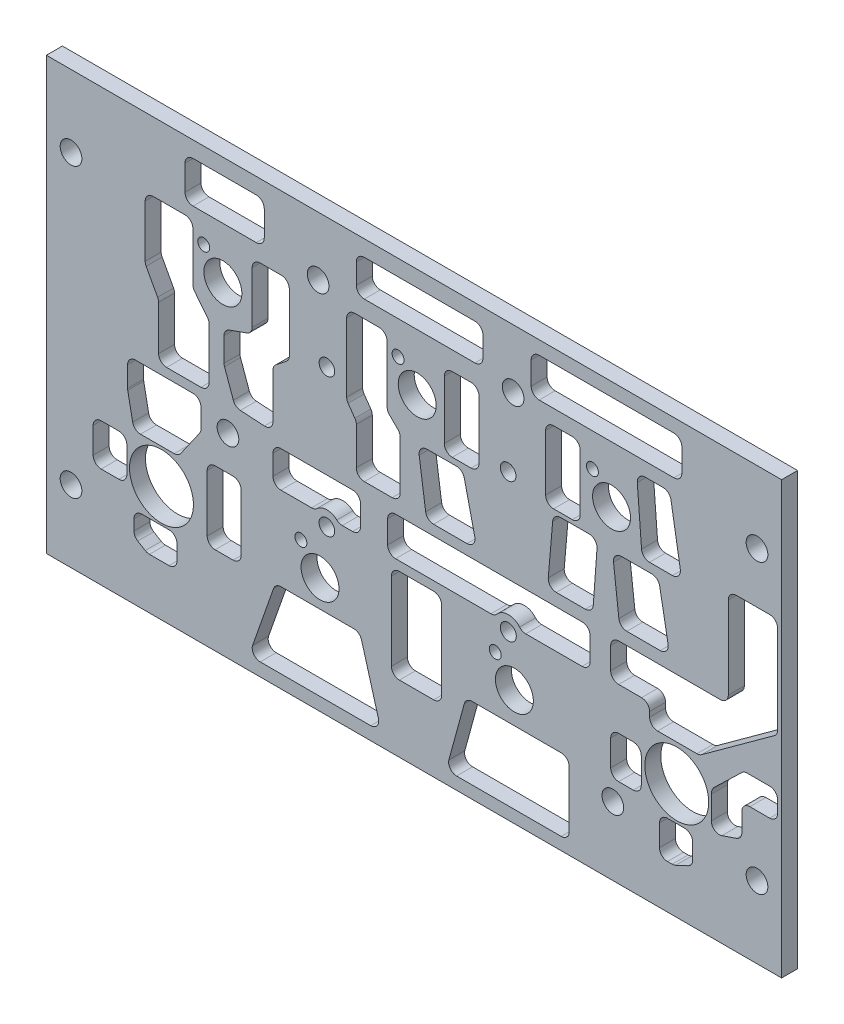
SolidWorks part; units mm, degrees
ref_plane "Front Plane" through (0, 0, 0) normal (0, 0, 1) x (1, 0, 0)
ref_plane "Top Plane" through (0, 0, 0) normal (0, 1, 0) x (1, 0, 0)
ref_plane "Right Plane" through (0, 0, 0) normal (1, 0, 0) x (0, 0, -1)
sketch "Sketch1" plane through (0, 0, 0) normal (0, 0, 1) x (1, 0, 0)
  line L4 (0, 85.725) -> (-146.05, 85.725)
  line L5 (-146.05, 85.725) -> (-146.05, 0)
  line L6 (-146.05, 0) -> (0, 0)
  line L7 (0, 0) -> (0, 85.725)
  line L8 (0, 85.725) -> (-146.05, 85.725)
  line L9 (-146.05, 85.725) -> (-146.05, 0)
  line L10 (-146.05, 0) -> (0, 0)
  line L11 (0, 0) -> (0, 85.725)
  dimension "D1" = 0
extrude "Backplate Body" add sketch "Sketch1" against normal blind 3.175
hole_wizard "#6 Clearance Hole1" positions "Sketch3" profile "Sketch2" hole size "#6" standard "ANSI Inch"
sketch "Sketch3" plane through (0, 0, -3.175) normal (0, 0, -1) x (-1, 0, 0)
  point P0 (4.8895, 71.4375)
  point P3 (53.34, 74.041)
  point P6 (92.075, 74.041)
  point P9 (141.1605, 71.4375)
  point P12 (109.982, 38.735)
  point P15 (141.1605, 14.2875)
  point P18 (33.528, 13.589)
  point P21 (4.8895, 14.2875)
sketch "Sketch2" plane through (-4.8895, 71.4375, -3.175) normal (1, 0, 0) x (0, 1, 0)
  line L0 (0, 0) -> (0, 13.9934)
  line L1 (0, 13.9934) -> (2.1526, 12.7)
  line L2 (2.1526, 12.7) -> (2.1526, 0)
  line L5 (2.1526, 0) -> (0, 0)
  line L10 (0, 13.9934) -> (-2.1526, 12.7) construction
  line L11 (0, -6.35) -> (0, 107.95) construction
  dimension "Hole Dia." = 4.3053
  dimension "Hole Depth" = 12.7
  dimension "Drill Angle" = 118
sketch "Sketch4" plane through (0, 0, -3.175) normal (0, 0, -1) x (-1, 0, 0)
  circle A0 centre (20.828, 22.987) radius 6.35
  circle A1 centre (123.19, 22.987) radius 6.35
  circle A2 centre (33.782, 64.135) radius 3.7703
  circle A3 centre (72.39, 64.135) radius 3.7703
  circle A4 centre (110.998, 64.135) radius 3.7703
  circle A5 centre (91.694, 22.987) radius 3.7703
  circle A6 centre (53.086, 22.987) radius 3.7703
  circle A7 centre (37.5823, 68.778) radius 1.1906
  circle A8 centre (76.1903, 68.778) radius 1.1906
  circle A9 centre (114.7983, 68.778) radius 1.1906
  circle A10 centre (56.8863, 27.63) radius 1.1906
  circle A11 centre (95.4943, 27.63) radius 1.1906
  dimension "D1" = 12.7
  dimension "D2" = 7.5406
  dimension "D3" = 2.3813
extrude "Switch Mount Holes" cut sketch "Sketch4" against normal through all
sketch "Sketch6" plane through (0, 0, -3.175) normal (0, 0, -1) x (-1, 0, 0)
  line L0 (0.7854, 59.7497) -> (0.7854, 42.2627)
  line L1 (1.4397, 40.9784) -> (15.8873, 30.4799)
  line L4 (16.8205, 30.1766) -> (24.6388, 30.1766)
  line L5 (26.2263, 31.7641) -> (26.2263, 32.7329)
  line L6 (27.8138, 34.3204) -> (32.3673, 34.3204)
  line L7 (33.9548, 35.9079) -> (33.9548, 40.2156)
  line L8 (32.3673, 41.8031) -> (12.1743, 41.8031)
  line L9 (10.5868, 43.3906) -> (10.5868, 59.7497)
  line L10 (8.9993, 61.3372) -> (2.3729, 61.3372)
  line L11 (21.4, 75.3506) -> (48.1668, 75.3506)
  line L12 (49.7543, 76.9381) -> (49.7543, 81.4624)
  line L13 (48.1668, 83.0499) -> (21.4, 83.0499)
  line L14 (19.8125, 81.4624) -> (19.8125, 76.9381)
  line L15 (59.3356, 80.9492) -> (59.3356, 76.9381)
  line L16 (60.9231, 75.3506) -> (82.8992, 75.3506)
  line L17 (84.4867, 76.9381) -> (84.4867, 80.9492)
  line L18 (82.8992, 82.5367) -> (60.9231, 82.5367)
  line L19 (28.672, 70.9074) -> (27.8272, 59.8641)
  line L20 (26.2443, 58.3977) -> (21.6898, 58.3977)
  line L21 (20.1244, 60.2489) -> (21.9848, 71.2922)
  line L22 (23.5503, 72.616) -> (27.0892, 72.616)
  line L23 (46.8767, 70.769) -> (46.8767, 59.6575)
  line L24 (45.2892, 58.07) -> (41.5893, 58.07)
  line L25 (40.0018, 59.6575) -> (40.0018, 70.769)
  line L26 (41.5893, 72.3565) -> (45.2892, 72.3565)
  line L27 (38.2576, 57.2789) -> (43.8996, 57.2789)
  line L28 (45.4813, 55.8276) -> (46.355, 45.6783)
  line L29 (44.7734, 43.9546) -> (38.997, 43.9546)
  line L30 (37.4137, 45.4268) -> (36.6743, 55.5761)
  line L31 (24.2194, 55.3227) -> (22.5486, 46.1448)
  line L32 (24.1104, 44.273) -> (30.7553, 44.273)
  line L33 (32.3322, 45.6779) -> (33.3948, 54.8558)
  line L34 (31.8178, 56.6259) -> (25.7812, 56.6259)
  line L35 (61.6963, 71.619) -> (65.4237, 71.619)
  line L36 (67.0112, 70.0315) -> (67.0112, 58.4598)
  line L37 (65.4237, 56.8723) -> (61.6963, 56.8723)
  line L38 (60.1088, 58.4598) -> (60.1088, 70.0315)
  line L39 (78.3684, 70.3657) -> (78.3684, 59.0552)
  line L40 (77.9034, 57.9327) -> (76.2306, 56.2599)
  line L41 (75.7657, 55.1374) -> (75.7657, 45.5421)
  line L42 (77.3532, 43.9546) -> (82.8992, 43.9546)
  line L43 (84.4867, 45.5421) -> (84.4867, 52.9982)
  line L44 (84.774, 53.9091) -> (86.1126, 55.8195)
  line L45 (86.3999, 56.7304) -> (86.3999, 70.3657)
  line L46 (84.8124, 71.9532) -> (79.9559, 71.9532)
  line L47 (64.5881, 55.7521) -> (70.4272, 55.7521)
  line L48 (71.9989, 53.9418) -> (70.7103, 44.8514)
  line L49 (69.1385, 43.4867) -> (62.4983, 43.4867)
  line L50 (60.9512, 45.4299) -> (63.041, 54.5203)
  line L51 (104.3617, 82.5367) -> (116.9306, 82.5367)
  line L52 (118.5181, 80.9492) -> (118.5181, 75.9239)
  line L53 (116.9306, 74.3364) -> (104.3617, 74.3364)
  line L54 (102.7742, 75.9239) -> (102.7742, 80.9492)
  line L55 (116.9515, 70.4508) -> (116.9515, 60.795)
  line L56 (116.6029, 59.8023) -> (114.0887, 56.6647)
  line L57 (113.7401, 55.6721) -> (113.7401, 45.5421)
  line L58 (115.3276, 43.9546) -> (122.1785, 43.9546)
  line L59 (123.766, 45.5421) -> (123.766, 54.3743)
  line L60 (123.9579, 55.131) -> (126.2372, 59.3351)
  line L61 (126.4292, 60.0918) -> (126.4292, 70.4508)
  line L62 (124.8417, 72.0383) -> (118.539, 72.0383)
  line L63 (105.1722, 69.6262) -> (105.1722, 59.351)
  line L64 (106.2241, 57.8565) -> (109.7117, 56.6066)
  line L65 (110.7636, 55.1122) -> (110.7636, 50.368)
  line L66 (110.6706, 49.8324) -> (108.9167, 44.9385)
  line L67 (107.5209, 43.8896) -> (102.7372, 43.5917)
  line L68 (101.051, 45.1761) -> (101.051, 54.0148)
  line L69 (100.4562, 55.2536) -> (98.3918, 56.9078)
  line L70 (97.797, 58.1467) -> (97.797, 69.6262)
  line L71 (99.3845, 71.2137) -> (103.5847, 71.2137)
  line L72 (39.6269, 33.7908) -> (50.842, 33.7908)
  line L73 (78.2665, 35.3783) -> (78.2665, 39.8664)
  line L74 (76.679, 41.4539) -> (39.6269, 41.4539)
  line L75 (38.0394, 39.8664) -> (38.0394, 35.3783)
  line L76 (83.642, 39.7608) -> (83.642, 35.7883)
  line L77 (85.2295, 34.2008) -> (87.2841, 34.2008)
  line L78 (101.051, 35.7883) -> (101.051, 39.7608)
  line L79 (99.4635, 41.3483) -> (85.2295, 41.3483)
  line L80 (115.3458, 40.5393) -> (115.3458, 36.8018)
  line L81 (115.6328, 35.8915) -> (119.3681, 30.5551)
  line L82 (120.6686, 29.8779) -> (127.3572, 29.8779)
  line L83 (128.9152, 31.1612) -> (129.8894, 36.1507)
  line L84 (129.9188, 36.4549) -> (129.9188, 40.5393)
  line L85 (128.3313, 42.1268) -> (116.9333, 42.1268)
  line L86 (0.7854, 30.2344) -> (0.7854, 27.9015)
  line L87 (2.3729, 26.314) -> (6.3156, 26.314)
  line L88 (7.9031, 24.7265) -> (7.9031, 21.0409)
  line L91 (13.9709, 20.0555) -> (13.9709, 24.6575)
  line L92 (13.3361, 26.1523) -> (7.9216, 31.3768)
  line L93 (6.8193, 31.8219) -> (2.3729, 31.8219)
  line L94 (18.5828, 10.0167) -> (21.0703, 8.8579)
  line L95 (21.7407, 8.7095) -> (22.6736, 8.7095)
  line L96 (24.2611, 10.297) -> (24.2611, 14.5475)
  line L97 (22.6736, 16.135) -> (19.2531, 16.135)
  line L98 (17.6656, 14.5475) -> (17.6656, 11.4558)
  line L99 (27.8819, 24.3095) -> (27.8819, 19.1834)
  line L100 (29.4694, 17.5959) -> (32.3673, 17.5959)
  line L101 (33.9548, 19.1834) -> (33.9548, 24.3095)
  line L102 (32.3673, 25.897) -> (29.4694, 25.897)
  line L103 (43.7793, 2.4684) -> (64.5682, 2.4684)
  line L104 (66.0995, 4.4745) -> (63.0373, 15.675)
  line L105 (61.506, 16.8438) -> (43.7793, 16.8438)
  line L106 (42.1918, 15.2563) -> (42.1918, 4.0559)
  line L107 (67.5359, 30.389) -> (67.5359, 14.8805)
  line L108 (69.1234, 13.293) -> (75.9295, 13.293)
  line L109 (77.517, 14.8805) -> (77.517, 30.389)
  line L110 (75.9295, 31.9765) -> (69.1234, 31.9765)
  line L111 (83.4506, 16.4411) -> (80.1004, 4.6154)
  line L112 (81.6278, 2.5952) -> (103.578, 2.5952)
  line L113 (105.0761, 4.708) -> (100.9298, 16.5336)
  line L114 (99.4317, 17.5959) -> (84.978, 17.5959)
  line L115 (114.1111, 30.2647) -> (114.1111, 18.9987)
  line L116 (112.5236, 17.4112) -> (108.9618, 17.4112)
  line L117 (107.3743, 18.9987) -> (107.3743, 30.2647)
  line L118 (108.9618, 31.8522) -> (112.5236, 31.8522)
  line L119 (130.0717, 26.6877) -> (130.0717, 21.5613)
  line L120 (131.6592, 19.9738) -> (135.1785, 19.9738)
  line L121 (136.766, 21.5613) -> (136.766, 26.6877)
  line L122 (135.1785, 28.2752) -> (131.6592, 28.2752)
  line L123 (121.6942, 16.2539) -> (127.0772, 16.2539)
  line L124 (128.6647, 14.6664) -> (128.6647, 12.5851)
  line L125 (127.9016, 11.2285) -> (126.4171, 10.3264)
  line L126 (125.5927, 10.0955) -> (121.6942, 10.0955)
  line L127 (120.1067, 11.683) -> (120.1067, 14.6664)
  line L129 (57.7397, 33.7908) -> (76.679, 33.7908)
  line L130 (93.3749, 34.2008) -> (99.4635, 34.2008)
  line L131 (8.9787, 19.5382) -> (11.8715, 18.5528)
  line L132 (0.0043, 85.727) -> (146.0543, 85.727) construction
  line L133 (0.0043, 85.727) -> (0.0043, 0.002) construction
  arc A0 (121.6942, 10.0955) -> (120.1067, 11.683) centre (121.6942, 11.683) cw
  arc A1 (126.4171, 10.3264) -> (125.5927, 10.0955) centre (125.5927, 11.683) cw
  arc A2 (128.6647, 12.5851) -> (127.9016, 11.2285) centre (127.0772, 12.5851) cw
  arc A3 (127.0772, 16.2539) -> (128.6647, 14.6664) centre (127.0772, 14.6664) cw
  arc A4 (136.766, 26.6877) -> (135.1785, 28.2752) centre (135.1785, 26.6877) ccw
  arc A5 (121.6942, 16.2539) -> (120.1067, 14.6664) centre (121.6942, 14.6664) ccw
  arc A6 (135.1785, 19.9738) -> (136.766, 21.5613) centre (135.1785, 21.5613) ccw
  arc A7 (130.0717, 21.5613) -> (131.6592, 19.9738) centre (131.6592, 21.5613) ccw
  arc A8 (130.0717, 26.6877) -> (131.6592, 28.2752) centre (131.6592, 26.6877) cw
  arc A9 (107.3743, 30.2647) -> (108.9618, 31.8522) centre (108.9618, 30.2647) cw
  arc A10 (108.9618, 17.4112) -> (107.3743, 18.9987) centre (108.9618, 18.9987) cw
  arc A11 (114.1111, 18.9987) -> (112.5236, 17.4112) centre (112.5236, 18.9987) cw
  arc A12 (114.1111, 30.2647) -> (112.5236, 31.8522) centre (112.5236, 30.2647) ccw
  arc A13 (103.578, 2.5952) -> (105.0761, 4.708) centre (103.578, 4.1827) ccw
  arc A14 (100.9298, 16.5336) -> (99.4317, 17.5959) centre (99.4317, 16.0084) ccw
  arc A15 (80.1004, 4.6154) -> (81.6278, 2.5952) centre (81.6278, 4.1827) ccw
  arc A16 (83.4506, 16.4411) -> (84.978, 17.5959) centre (84.978, 16.0084) cw
  arc A17 (77.517, 30.389) -> (75.9295, 31.9765) centre (75.9295, 30.389) ccw
  arc A18 (75.9295, 13.293) -> (77.517, 14.8805) centre (75.9295, 14.8805) ccw
  arc A19 (67.5359, 14.8805) -> (69.1234, 13.293) centre (69.1234, 14.8805) ccw
  arc A20 (43.7793, 16.8438) -> (42.1918, 15.2563) centre (43.7793, 15.2563) ccw
  arc A21 (63.0373, 15.675) -> (61.506, 16.8438) centre (61.506, 15.2563) ccw
  arc A22 (67.5359, 30.389) -> (69.1234, 31.9765) centre (69.1234, 30.389) cw
  arc A23 (64.5682, 2.4684) -> (66.0995, 4.4745) centre (64.5682, 4.0559) ccw
  arc A24 (43.7793, 2.4684) -> (42.1918, 4.0559) centre (43.7793, 4.0559) cw
  arc A25 (32.3673, 17.5959) -> (33.9548, 19.1834) centre (32.3673, 19.1834) ccw
  arc A26 (33.9548, 24.3095) -> (32.3673, 25.897) centre (32.3673, 24.3095) ccw
  arc A27 (27.8819, 19.1834) -> (29.4694, 17.5959) centre (29.4694, 19.1834) ccw
  arc A28 (27.8819, 24.3095) -> (29.4694, 25.897) centre (29.4694, 24.3095) cw
  arc A29 (19.2531, 16.135) -> (17.6656, 14.5475) centre (19.2531, 14.5475) ccw
  arc A30 (24.2611, 14.5475) -> (22.6736, 16.135) centre (22.6736, 14.5475) ccw
  arc A31 (22.6736, 8.7095) -> (24.2611, 10.297) centre (22.6736, 10.297) ccw
  arc A32 (21.0703, 8.8579) -> (21.7407, 8.7095) centre (21.7407, 10.297) ccw
  arc A33 (18.5828, 10.0167) -> (17.6656, 11.4558) centre (19.2531, 11.4558) cw
  arc A34 (7.9216, 31.3768) -> (6.8193, 31.8219) centre (6.8193, 30.2344) ccw
  arc A37 (13.9709, 24.6575) -> (13.3361, 26.1523) centre (11.8938, 24.6575) ccw
  arc A39 (6.3156, 26.314) -> (7.9031, 24.7265) centre (6.3156, 24.7265) cw
  arc A40 (0.7854, 27.9015) -> (2.3729, 26.314) centre (2.3729, 27.9015) ccw
  arc A41 (0.7854, 30.2344) -> (2.3729, 31.8219) centre (2.3729, 30.2344) cw
  arc A42 (129.9188, 40.5393) -> (128.3313, 42.1268) centre (128.3313, 40.5393) ccw
  arc A43 (127.3572, 29.8779) -> (128.9152, 31.1612) centre (127.3572, 31.4654) ccw
  arc A44 (129.8894, 36.1507) -> (129.9188, 36.4549) centre (128.3313, 36.4549) ccw
  arc A45 (119.3681, 30.5551) -> (120.6686, 29.8779) centre (120.6686, 31.4654) ccw
  arc A46 (115.3458, 36.8018) -> (115.6328, 35.8915) centre (116.9333, 36.8018) ccw
  arc A47 (115.3458, 40.5393) -> (116.9333, 42.1268) centre (116.9333, 40.5393) cw
  arc A48 (99.4635, 34.2008) -> (101.051, 35.7883) centre (99.4635, 35.7883) ccw
  arc A49 (101.051, 39.7608) -> (99.4635, 41.3483) centre (99.4635, 39.7608) ccw
  arc A50 (83.642, 35.7883) -> (85.2295, 34.2008) centre (85.2295, 35.7883) ccw
  arc A51 (83.642, 39.7608) -> (85.2295, 41.3483) centre (85.2295, 39.7608) cw
  arc A52 (39.6269, 41.4539) -> (38.0394, 39.8664) centre (39.6269, 39.8664) ccw
  arc A53 (78.2665, 39.8664) -> (76.679, 41.4539) centre (76.679, 39.8664) ccw
  arc A54 (76.679, 33.7908) -> (78.2665, 35.3783) centre (76.679, 35.3783) ccw
  arc A55 (39.6269, 33.7908) -> (38.0394, 35.3783) centre (39.6269, 35.3783) cw
  arc A56 (97.797, 69.6262) -> (99.3845, 71.2137) centre (99.3845, 69.6262) cw
  arc A57 (98.3918, 56.9078) -> (97.797, 58.1467) centre (99.3845, 58.1467) cw
  arc A58 (102.7372, 43.5917) -> (101.051, 45.1761) centre (102.6385, 45.1761) cw
  arc A59 (101.051, 54.0148) -> (100.4562, 55.2536) centre (99.4635, 54.0148) ccw
  arc A60 (110.7636, 50.368) -> (110.6706, 49.8324) centre (109.1761, 50.368) cw
  arc A61 (108.9167, 44.9385) -> (107.5209, 43.8896) centre (107.4222, 45.4741) cw
  arc A62 (109.7117, 56.6066) -> (110.7636, 55.1122) centre (109.1761, 55.1122) cw
  arc A63 (105.1722, 59.351) -> (106.2241, 57.8565) centre (106.7597, 59.351) ccw
  arc A64 (126.4292, 70.4508) -> (124.8417, 72.0383) centre (124.8417, 70.4508) ccw
  arc A65 (126.2372, 59.3351) -> (126.4292, 60.0918) centre (124.8417, 60.0918) ccw
  arc A66 (105.1722, 69.6262) -> (103.5847, 71.2137) centre (103.5847, 69.6262) ccw
  arc A67 (122.1785, 43.9546) -> (123.766, 45.5421) centre (122.1785, 45.5421) ccw
  arc A68 (113.7401, 45.5421) -> (115.3276, 43.9546) centre (115.3276, 45.5421) ccw
  arc A69 (114.0887, 56.6647) -> (113.7401, 55.6721) centre (115.3276, 55.6721) ccw
  arc A70 (123.766, 54.3743) -> (123.9579, 55.131) centre (125.3535, 54.3743) cw
  arc A71 (116.9515, 60.795) -> (116.6029, 59.8023) centre (115.364, 60.795) cw
  arc A72 (116.9515, 70.4508) -> (118.539, 72.0383) centre (118.539, 70.4508) cw
  arc A73 (104.3617, 74.3364) -> (102.7742, 75.9239) centre (104.3617, 75.9239) cw
  arc A74 (118.5181, 75.9239) -> (116.9306, 74.3364) centre (116.9306, 75.9239) cw
  arc A75 (116.9306, 82.5367) -> (118.5181, 80.9492) centre (116.9306, 80.9492) cw
  arc A76 (104.3617, 82.5367) -> (102.7742, 80.9492) centre (104.3617, 80.9492) ccw
  arc A77 (62.4983, 43.4867) -> (60.9512, 45.4299) centre (62.4983, 45.0742) cw
  arc A78 (70.7103, 44.8514) -> (69.1385, 43.4867) centre (69.1385, 45.0742) cw
  arc A79 (70.4272, 55.7521) -> (71.9989, 53.9418) centre (70.4272, 54.1646) cw
  arc A80 (86.3999, 70.3657) -> (84.8124, 71.9532) centre (84.8124, 70.3657) ccw
  arc A81 (64.5881, 55.7521) -> (63.041, 54.5203) centre (64.5881, 54.1646) ccw
  arc A82 (86.1126, 55.8195) -> (86.3999, 56.7304) centre (84.8124, 56.7304) ccw
  arc A83 (82.8992, 43.9546) -> (84.4867, 45.5421) centre (82.8992, 45.5421) ccw
  arc A84 (75.7657, 45.5421) -> (77.3532, 43.9546) centre (77.3532, 45.5421) ccw
  arc A85 (65.4237, 71.619) -> (67.0112, 70.0315) centre (65.4237, 70.0315) cw
  arc A86 (61.6963, 71.619) -> (60.1088, 70.0315) centre (61.6963, 70.0315) ccw
  arc A87 (76.2306, 56.2599) -> (75.7657, 55.1374) centre (77.3532, 55.1374) ccw
  arc A88 (84.4867, 52.9982) -> (84.774, 53.9091) centre (86.0742, 52.9982) cw
  arc A89 (78.3684, 59.0552) -> (77.9034, 57.9327) centre (76.7809, 59.0552) cw
  arc A90 (78.3684, 70.3657) -> (79.9559, 71.9532) centre (79.9559, 70.3657) cw
  arc A91 (61.6963, 56.8723) -> (60.1088, 58.4598) centre (61.6963, 58.4598) cw
  arc A92 (67.0112, 58.4598) -> (65.4237, 56.8723) centre (65.4237, 58.4598) cw
  arc A93 (33.3948, 54.8558) -> (31.8178, 56.6259) centre (31.8178, 55.0384) ccw
  arc A94 (30.7553, 44.273) -> (32.3322, 45.6779) centre (30.7553, 45.8605) ccw
  arc A95 (22.5486, 46.1448) -> (24.1104, 44.273) centre (24.1104, 45.8605) ccw
  arc A96 (24.2194, 55.3227) -> (25.7812, 56.6259) centre (25.7812, 55.0384) cw
  arc A97 (46.355, 45.6783) -> (44.7734, 43.9546) centre (44.7734, 45.5421) cw
  arc A98 (38.997, 43.9546) -> (37.4137, 45.4268) centre (38.997, 45.5421) cw
  arc A99 (43.8996, 57.2789) -> (45.4813, 55.8276) centre (43.8996, 55.6914) cw
  arc A100 (38.2576, 57.2789) -> (36.6743, 55.5761) centre (38.2576, 55.6914) ccw
  arc A101 (40.0018, 70.769) -> (41.5893, 72.3565) centre (41.5893, 70.769) cw
  arc A102 (41.5893, 58.07) -> (40.0018, 59.6575) centre (41.5893, 59.6575) cw
  arc A103 (46.8767, 59.6575) -> (45.2892, 58.07) centre (45.2892, 59.6575) cw
  arc A104 (21.9848, 71.2922) -> (23.5503, 72.616) centre (23.5503, 71.0285) cw
  arc A105 (21.6898, 58.3977) -> (20.1244, 60.2489) centre (21.6898, 59.9852) cw
  arc A106 (46.8767, 70.769) -> (45.2892, 72.3565) centre (45.2892, 70.769) ccw
  arc A107 (27.8272, 59.8641) -> (26.2443, 58.3977) centre (26.2443, 59.9852) cw
  arc A108 (28.672, 70.9074) -> (27.0892, 72.616) centre (27.0892, 71.0285) ccw
  arc A109 (84.4867, 80.9492) -> (82.8992, 82.5367) centre (82.8992, 80.9492) ccw
  arc A110 (59.3356, 76.9381) -> (60.9231, 75.3506) centre (60.9231, 76.9381) ccw
  arc A111 (82.8992, 75.3506) -> (84.4867, 76.9381) centre (82.8992, 76.9381) ccw
  arc A112 (10.5868, 59.7497) -> (8.9993, 61.3372) centre (8.9993, 59.7497) ccw
  arc A113 (12.1743, 41.8031) -> (10.5868, 43.3906) centre (12.1743, 43.3906) cw
  arc A114 (32.3673, 34.3204) -> (33.9548, 35.9079) centre (32.3673, 35.9079) ccw
  arc A115 (33.9548, 40.2156) -> (32.3673, 41.8031) centre (32.3673, 40.2156) ccw
  arc A116 (24.6388, 30.1766) -> (26.2263, 31.7641) centre (24.6388, 31.7641) ccw
  arc A117 (26.2263, 32.7329) -> (27.8138, 34.3204) centre (27.8138, 32.7329) cw
  arc A118 (15.8873, 30.4799) -> (16.8205, 30.1766) centre (16.8205, 31.7641) ccw
  arc A119 (59.3356, 80.9492) -> (60.9231, 82.5367) centre (60.9231, 80.9492) cw
  arc A120 (0.7854, 42.2627) -> (1.4397, 40.9784) centre (2.3729, 42.2627) ccw
  arc A121 (0.7854, 59.7497) -> (2.3729, 61.3372) centre (2.3729, 59.7497) cw
  arc A122 (49.7543, 81.4624) -> (48.1668, 83.0499) centre (48.1668, 81.4624) ccw
  arc A123 (48.1668, 75.3506) -> (49.7543, 76.9381) centre (48.1668, 76.9381) ccw
  arc A124 (19.8125, 76.9381) -> (21.4, 75.3506) centre (21.4, 76.9381) ccw
  arc A125 (21.4, 83.0499) -> (19.8125, 81.4624) centre (21.4, 81.4624) ccw
  arc A126 (56.5338, 34.3459) -> (52.048, 34.3459) centre (54.2909, 32.4258) ccw
  arc A127 (50.842, 33.7908) -> (52.048, 34.3459) centre (50.842, 35.3783) ccw
  arc A128 (57.7397, 33.7908) -> (56.5338, 34.3459) centre (57.7397, 35.3783) cw
  arc A129 (92.3069, 34.6138) -> (88.3521, 34.6138) centre (90.3295, 32.439) ccw
  arc A130 (92.3069, 34.6138) -> (93.3749, 34.2008) centre (93.3749, 35.7883) ccw
  arc A131 (88.3521, 34.6138) -> (87.2841, 34.2008) centre (87.2841, 35.7883) cw
  arc A132 (13.9709, 20.0555) -> (11.8715, 18.5528) centre (12.3834, 20.0555) cw
  arc A133 (7.9031, 21.0409) -> (8.9787, 19.5382) centre (9.4906, 21.0409) ccw
  circle A134 centre (90.3252, 59.937) radius 1.55
  circle A135 centre (54.3252, 59.937) radius 1.55
  circle A136 centre (90.3295, 32.439) radius 1.5548
  circle A137 centre (54.2909, 32.4258) radius 1.5861
  point P244 (101.051, 43.4867)
  point P347 (84.4867, 82.5367)
  point P370 (0.7854, 41.4539)
  point P394 (92.6823, 34.2008)
  dimension "D1" = 1.5875
  dimension "D2" = 1.5875
  dimension "D3" = 1.5875
  dimension "D4" = 1.5875
  dimension "D5" = 1.5875
extrude "Backlighting LED Holes" cut sketch "Sketch6" against normal through all
